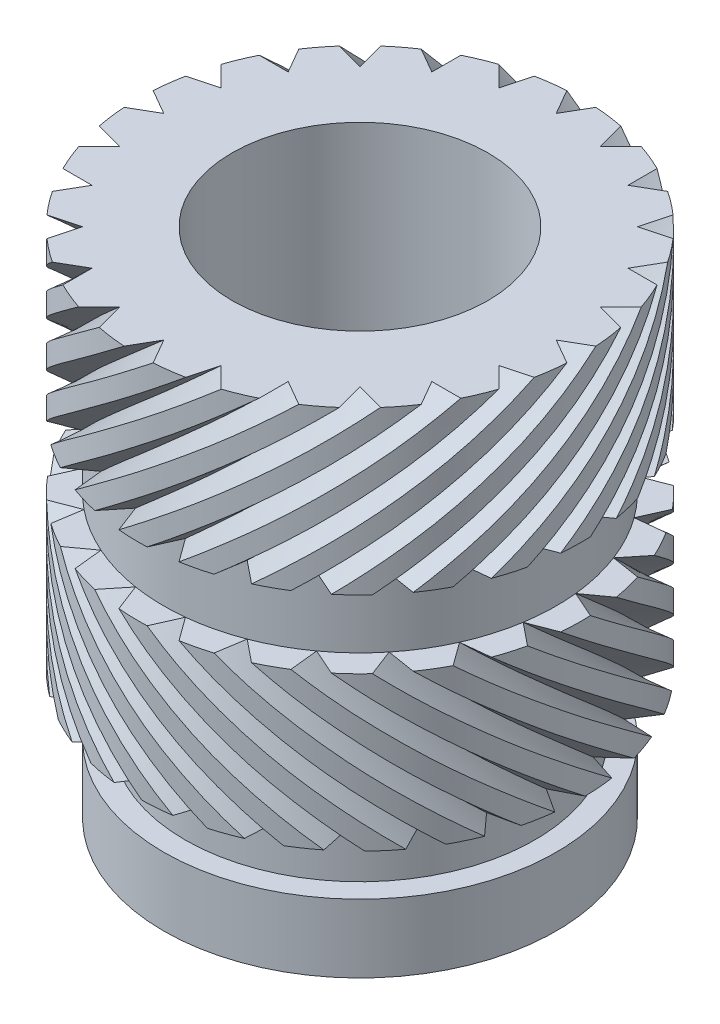
SolidWorks part; units mm, degrees
ref_plane "Front Plane" through (0, 0, 0) normal (0, 0, 1) x (1, 0, 0)
ref_plane "Top Plane" through (0, 0, 0) normal (0, 1, 0) x (1, 0, 0)
ref_plane "Right Plane" through (0, 0, 0) normal (1, 0, 0) x (0, 0, -1)
sketch "Sketch1" plane through (0, 0, 0) normal (0, 0, 1) x (1, 0, 0)
  line L0 (0, 0) -> (0, 6) construction
  line L1 (1.5, 6) -> (1.5, 0)
  line L2 (1.5, 0) -> (2.3, 0)
  line L3 (2.3, 0) -> (2.3, 0.8)
  line L4 (2.3, 0.8) -> (2.05, 0.8)
  line L5 (2.05, 0.8) -> (2.05, 1.5)
  line L6 (2.05, 1.5) -> (2.6, 1.5)
  line L7 (2.6, 1.5) -> (2.6, 3.3)
  line L8 (2.6, 3.3) -> (2.3, 3.3)
  line L9 (2.3, 3.3) -> (2.3, 4.1)
  line L10 (2.3, 4.1) -> (2.6, 4.1)
  line L11 (2.6, 4.1) -> (2.6, 6)
  line L12 (2.6, 6) -> (1.5, 6)
  point P15 (12.9547, 14.3272)
  point P16 (12.9547, 3.2263)
  point P17 (12.9547, 17.6198)
  point P18 (12.2021, 1.4154)
  point P19 (0, 0)
  point P20 (0, 0)
  point P21 (12.2166, 5.1867)
  point P22 (2.3142, 1.0595)
  point P23 (2.3063, 0.4506)
  point P24 (2.9811, 0)
  point P25 (2.0333, 0.8)
  dimension "D1" = 1.9
  dimension "D2" = 6
  dimension "D3" = 3
  dimension "D4" = 5.2
  dimension "D5" = 0.8
  dimension "D6" = 1.8
  dimension "D7" = 0.8
  dimension "D8" = 4.6
  dimension "D9" = 4.1
revolve "Revolve1" add sketch "Sketch1" angle 360 about L0
sketch "Sketch2" plane through (0, 6, 0) normal (0, 1, 0) x (1, 0, 0)
  circle A0 centre (0, 0) radius 2.3 construction
  circle A1 centre (0, 0) radius 2.3
curve "Helix/Spiral1" pitch 12.6667 height 1.9 radius 2.3 centre (0, 6, 0) axis (0, -1, 0) start towards (0, 0, 1)
sketch "Sketch3" plane through (0, 6, 0) normal (0, 1, 0) x (1, 0, 0)
  line L0 (0, 0) -> (-3.199, 0) construction
  line L1 (-2.8196, 0) -> (-2.8196, 0.3)
  line L2 (-2.8196, 0.3) -> (-2.3, 0)
  line L3 (-2.3, 0) -> (-2.8196, -0.3)
  line L4 (-2.8196, -0.3) -> (-2.8196, 0)
  spline S0 degree 3 poles (-2.3, 0) (-2.3, 0.2403) (-2.2236, 0.7228) (-1.8918, 1.3741) (-1.5463, 1.7195) (-1.3519, 1.8607) knots 0 0 0 0 0.333333 0.666667 1 1 1 1 construction
  point P5 (-2.3747, 0)
  dimension "D1" = 60
  dimension "D2" = 0.6
sweep "Cut-Sweep1" cut profiles "Sketch3" path "Helix/Spiral1"
pattern_circular "CirPattern1" count 24 over 360 about axis through (0, 0, 0) along (0, -1, 0) of "Cut-Sweep1"
ref_plane "Plane1" through (0, 3.7, 0) normal (0, -1, 0) x (-1, 0, 0)
mirror "Mirror1" about plane through (0, 3.7, 0) normal (0, -1, 0) of "CirPattern1"
